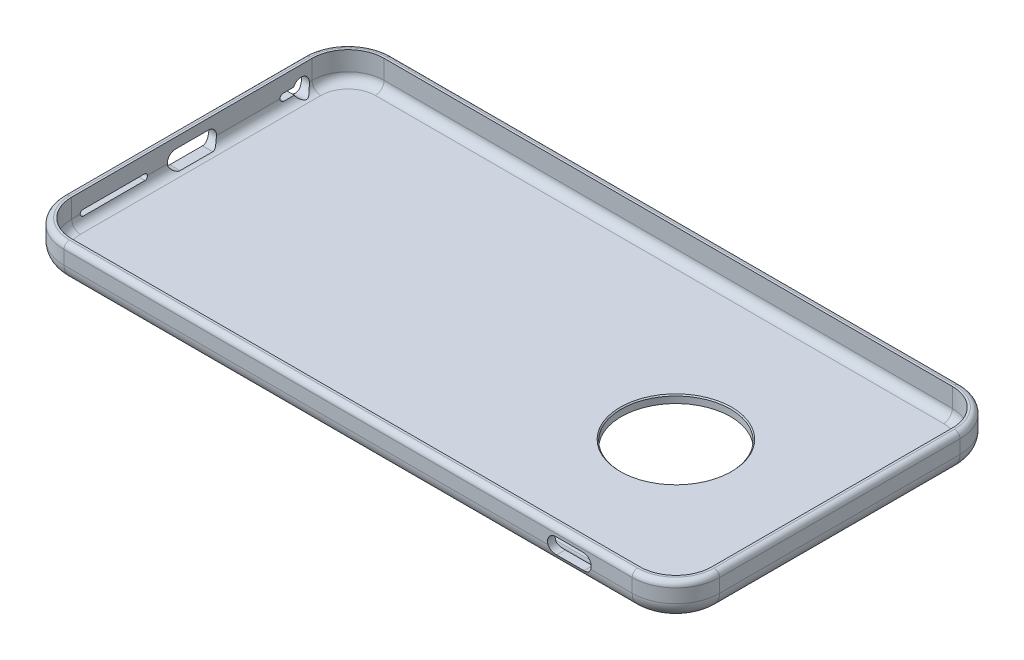
SolidWorks part; units mm, degrees
ref_plane "Front Plane" through (0, 0, 0) normal (0, 0, 1) x (1, 0, 0)
ref_plane "Top Plane" through (0, 0, 0) normal (0, 1, 0) x (1, 0, 0)
ref_plane "Right Plane" through (0, 0, 0) normal (1, 0, 0) x (0, 0, -1)
sketch "Sketch1" plane through (0, 0, 0) normal (0, 1, 0) x (1, 0, 0)
  line L1 (-76.2, -38.1) -> (76.2, -38.1)
  line L2 (-76.2, -38.1) -> (-76.2, 38.1)
  line L3 (-76.2, 38.1) -> (76.2, 38.1)
  line L4 (76.2, -38.1) -> (76.2, 38.1)
  dimension "D1" = 152.4
  dimension "D2" = 76.2
  dimension "D3" = 38.1
  dimension "D4" = 76.2
extrude "Boss-Extrude1" add sketch "Sketch1" along normal blind 8.255
fillet "Fillet1" radius 10.16 4 edges at (-76.2, 4.1275, -38.1) (76.2, 4.1275, -38.1) (76.2, 4.1275, 38.1) (-76.2, 4.1275, 38.1)
fillet "Fillet2" radius 3.81 8 edges at (73.2242, 0, -35.1242) (76.2, 0, 0) (73.2242, 0, 35.1242) (0, 0, 38.1) (-73.2242, 0, 35.1242) (-76.2, 0, 0) (-73.2242, 0, -35.1242) (0, 0, -38.1)
fillet "Fillet3" radius 1.27 8 edges at (73.2242, 8.255, -35.1242) (76.2, 8.255, 0) (73.2242, 8.255, 35.1242) (0, 8.255, 38.1) (-73.2242, 8.255, 35.1242) (-76.2, 8.255, 0) (-73.2242, 8.255, -35.1242) (0, 8.255, -38.1)
shell "Shell1" thickness 1.778 removed face at (0, 8.255, 0)
sketch "Sketch2" plane through (0, 0, 0) normal (0, -1, 0) x (1, 0, 0)
  circle A0 centre (38.1, 0) radius 12.7
  dimension "D1" = 25.4
  dimension "D2" = 38.1
extrude "Cut-Extrude1" cut sketch "Sketch2" against normal through all
sketch "Sketch3" plane through (0, 0, 0) normal (0, -1, 0) x (1, 0, 0)
  line L0 (66.04, -12.7) -> (66.04, -24.13) construction
  line L1 (69.215, -12.7) -> (69.215, -24.13)
  line L2 (62.865, -12.7) -> (62.865, -24.13)
  arc A0 (69.215, -12.7) -> (62.865, -12.7) centre (66.04, -12.7) ccw
  arc A1 (62.865, -24.13) -> (69.215, -24.13) centre (66.04, -24.13) ccw
  circle A2 centre (38.1, 0) radius 12.7 construction
  point P2 (66.04, -18.415)
  dimension "D1" = 12.7
  dimension "D2" = 11.43
  dimension "D3" = 3.175
  dimension "D4" = 27.94
extrude "Cut-Extrude2" [suppressed] cut sketch "Sketch3" against normal through all
sketch "Sketch4" plane through (0, 0, 0) normal (0, 0, 1) x (1, 0, 0)
  line L0 (54.61, 4.445) -> (48.26, 4.445) construction
  line L1 (54.61, 2.54) -> (48.26, 2.54)
  line L2 (54.61, 6.35) -> (48.26, 6.35)
  line L3 (74.93, 8.255) -> (66.04, 8.255) construction
  line L4 (76.2, 6.985) -> (76.2, 3.81) construction
  arc A0 (54.61, 2.54) -> (54.61, 6.35) centre (54.61, 4.445) ccw
  arc A1 (48.26, 6.35) -> (48.26, 2.54) centre (48.26, 4.445) ccw
  point P2 (51.435, 4.445)
  dimension "D1" = 1.905
  dimension "D2" = 6.35
  dimension "D3" = 3.81
  dimension "D4" = 21.59
extrude "Cut-Extrude3" cut sketch "Sketch4" along normal through all
sketch "Sketch5" plane through (0, 0, 0) normal (1, 0, 0) x (0, 0, -1)
  line L0 (3.81, 3.937) -> (-3.81, 3.937) construction
  line L1 (3.81, 2.032) -> (-3.81, 2.032)
  line L2 (3.81, 5.842) -> (-3.81, 5.842)
  line L3 (-27.94, 0) -> (27.94, 0) construction
  arc A0 (3.81, 2.032) -> (3.81, 5.842) centre (3.81, 3.937) ccw
  arc A1 (-3.81, 5.842) -> (-3.81, 2.032) centre (-3.81, 3.937) ccw
  point P2 (0, 3.937)
  dimension "D2" = 3.81
  dimension "D3" = 1.905
  dimension "D1" = 7.62
  dimension "D4" = 3.937
extrude "Cut-Extrude4" cut sketch "Sketch5" against normal through all
sketch "Sketch6" plane through (0, 0, 0) normal (1, 0, 0) x (0, 0, -1)
  line L0 (-10.964, 3.81) -> (-25.315, 3.81) construction
  line L1 (-10.964, 3.175) -> (-25.315, 3.175)
  line L2 (-10.964, 4.445) -> (-25.315, 4.445)
  line L3 (-27.94, 0) -> (27.94, 0) construction
  arc A0 (-10.964, 3.175) -> (-10.964, 4.445) centre (-10.964, 3.81) ccw
  arc A1 (-25.315, 4.445) -> (-25.315, 3.175) centre (-25.315, 3.81) ccw
  point P2 (-18.1395, 3.81)
  dimension "D1" = 0.635
  dimension "D3" = 14.351
  dimension "D2" = 3.175
extrude "Cut-Extrude5" cut sketch "Sketch6" against normal through all
sketch "Sketch7" plane through (0, 0, 0) normal (1, 0, 0) x (0, 0, -1)
  line L0 (25.4, 3.81) -> (21.209, 3.81) construction
  line L1 (25.4, 3.048) -> (21.209, 3.048)
  line L2 (25.4, 4.572) -> (21.209, 4.572)
  line L3 (-27.94, 0) -> (27.94, 0) construction
  line L4 (38.1, 3.81) -> (38.1, 6.985) construction
  arc A0 (25.4, 3.048) -> (25.4, 4.572) centre (25.4, 3.81) ccw
  arc A1 (21.209, 4.572) -> (21.209, 3.048) centre (21.209, 3.81) ccw
  point P2 (23.3045, 3.81)
  dimension "D1" = 0.762
  dimension "D2" = 4.191
  dimension "D3" = 3.81
  dimension "D4" = 12.7
extrude "Cut-Extrude6" cut sketch "Sketch7" against normal through all
sketch "Sketch8" plane through (0, 0, 0) normal (1, 0, 0) x (0, 0, -1)
  circle A0 centre (25.4, 3.81) radius 1.905
  arc A1 (26.162, 3.81) -> (25.4, 4.572) centre (25.4, 3.81) ccw construction
  dimension "D1" = 3.81
extrude "Cut-Extrude7" cut sketch "Sketch8" against normal through all
chamfer "Chamfer1" distance 0.254 angle 45 1 edges at (38.1, 1.778, -12.7)
